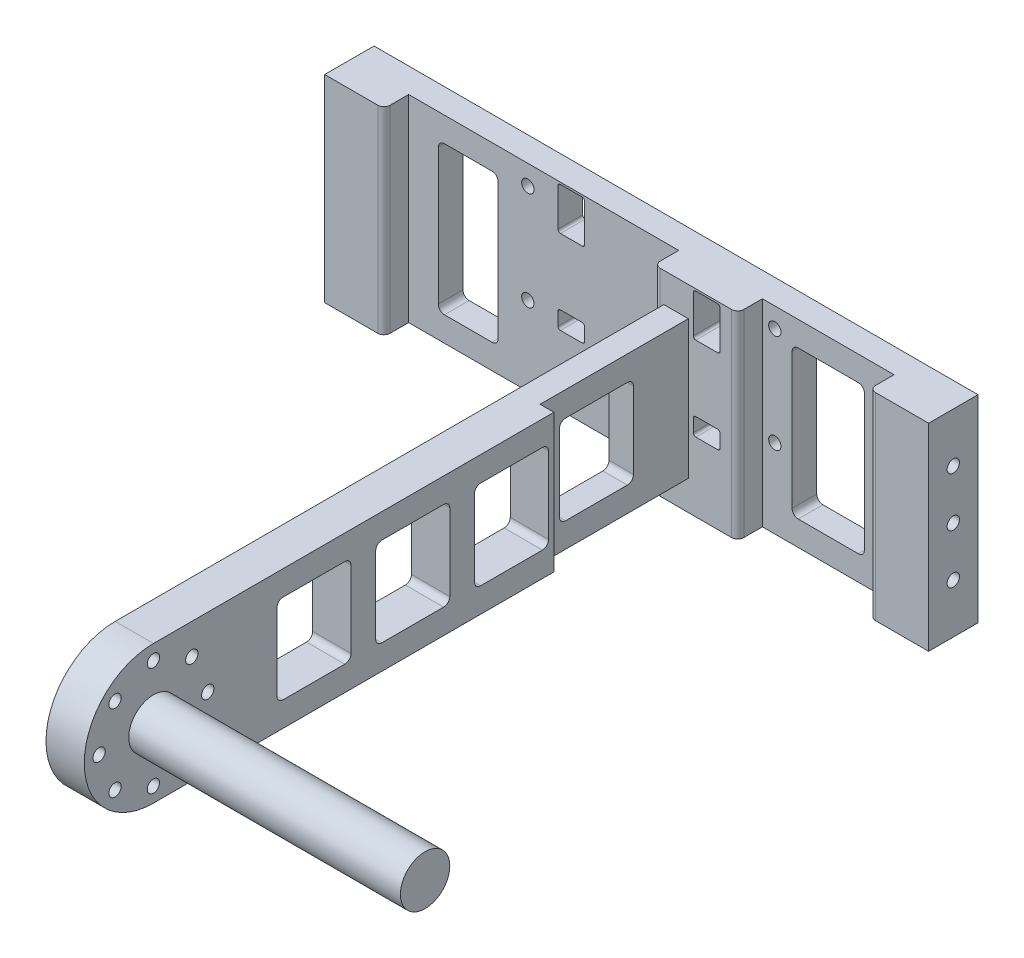
SolidWorks part; units mm, degrees
ref_plane "Front Plane" through (0, 0, 0) normal (0, 0, 1) x (1, 0, 0)
ref_plane "Top Plane" through (0, 0, 0) normal (0, 1, 0) x (1, 0, 0)
ref_plane "Right Plane" through (0, 0, 0) normal (1, 0, 0) x (0, 0, -1)
sketch "Sketch1" plane through (0, 0, 0) normal (0, 0, 1) x (1, 0, 0)
  line L1 (0, 0) -> (122.28, 0)
  line L2 (0, 0) -> (0, 40)
  line L3 (0, 40) -> (122.28, 40)
  line L4 (122.28, 0) -> (122.28, 40)
  dimension "D1" = 40
  dimension "D2" = 122.28
extrude "Boss-Extrude1" add sketch "Sketch1" along normal blind 10 contours L3 L4 L1 L2
sketch "Sketch2" plane through (0, 0, 10) normal (0, 0, 1) x (1, 0, 0)
  circle A0 centre (61.14, 20) radius 3.05
  circle A1 centre (76.14, 32.5) radius 1.25
  circle A2 centre (76.14, 15.5) radius 1.25
  dimension "D1" = 6.1
  dimension "D3" = 2.5
  dimension "D4" = 2.5
  dimension "D6" = 17
  dimension "D7" = 15
  dimension "D8" = 12.5
extrude "Cut-Extrude1" cut sketch "Sketch2" against normal blind 10
ref_plane "Plane1" through (61.14, 0, 0) normal (-1, 0, 0) x (0, 0, 1)
mirror "Mirror1" about plane through (61.14, 0, 0) normal (-1, 0, 0) of "Cut-Extrude1"
sketch "Sketch3" plane through (0, 0, 0) normal (-1, 0, 0) x (0, 0, 1)
  line L0 (10, 0) -> (10, 40) construction
  line L1 (10, 40) -> (0, 40) construction
  circle A0 centre (5, 20) radius 1.25
  circle A1 centre (5, 30) radius 1.25
  circle A2 centre (5, 10) radius 1.25
  dimension "D1" = 2.5
  dimension "D2" = 2.5
  dimension "D3" = 2.5
  dimension "D4" = 10
  dimension "D5" = 5
  dimension "D6" = 20
  dimension "D7" = 10
extrude "Cut-Extrude2" cut sketch "Sketch3" against normal blind 10
mirror "Mirror2" about plane through (61.14, 0, 0) normal (-1, 0, 0) of "Cut-Extrude2"
ref_plane "Plane2" through (76.43, 0, 0) normal (1, 0, 0) x (0, 0, -1)
sketch "Sketch4" plane through (76.43, 0, 0) normal (1, 0, 0) x (0, 0, -1)
  line L1 (-10, 0) -> (-10, 40) construction
  circle A0 centre (-121.1, 20) radius 5
  dimension "D1" = 10
  dimension "D2" = 111.1
extrude "Boss-Extrude2" add sketch "Sketch4" along normal blind 55 separate body
sketch "Sketch5" plane through (76.43, 0, 0) normal (-1, 0, 0) x (0, 0, 1)
  circle A0 centre (121.1, 20) radius 14
  dimension "D1" = 28
extrude "Boss-Extrude3" add sketch "Sketch5" along normal blind 7.75
sketch "Sketch6" plane through (68.68, 0, 0) normal (-1, 0, 0) x (0, 0, 1)
  circle A0 centre (121.1, 20) radius 5.05
  dimension "D1" = 10.1
ref_point "Point1"
ref_axis "Axis1" through (68.68, 20, 121.1) along (-1, 0, 0)
sketch "Sketch8" plane through (68.68, 0, 0) normal (-1, 0, 0) x (0, 0, 1)
  circle A0 centre (121.1, 9) radius 1.25
  circle A1 centre (121.1, 20) radius 14 construction
  dimension "D1" = 2.5
  dimension "D2" = 11
ref_plane "Plane3" through (0, 6, 0) normal (0, -1, 0) x (-1, 0, 0)
sketch "Sketch10" plane through (0, 6, 0) normal (0, -1, 0) x (-1, 0, 0)
  line L0 (-76.43, -107.1) -> (-76.43, -135.1) construction
  line L1 (-76.43, -121.1) -> (-68.68, -121.1)
  line L2 (-76.43, -121.1) -> (-76.43, -10)
  line L3 (-76.43, -10) -> (-68.68, -10)
  line L4 (-68.68, -121.1) -> (-68.68, -10)
  line L5 (0, -10) -> (-122.28, -10) construction
  dimension "D1" = 7.75
extrude "Boss-Extrude4" add sketch "Sketch10" against normal blind 28
extrude "Cut-Extrude6" cut sketch "Sketch8" against normal up to next
pattern_circular "CirPattern2" count 8 over 360 about axis through (68.68, 20, 121.1) along (-1, 0, 0) of "Cut-Extrude6"
extrude "Cut-Extrude7" cut sketch "Sketch6" against normal blind 2
sketch "Sketch11" plane through (70.68, 0, 0) normal (-1, 0, 0) x (0, 0, 1)
  circle A0 centre (121.1, 20) radius 2.675
  dimension "D1" = 5.35
extrude "Cut-Extrude8" cut sketch "Sketch11" against normal blind 3
sketch "Sketch14" plane through (76.43, 0, 0) normal (1, 0, 0) x (0, 0, -1)
  line L0 (-10, 34) -> (-121.1, 34) construction
  line L1 (-10, 34) -> (-40, 34)
  line L2 (-10, 34) -> (-10, 6)
  line L3 (-10, 6) -> (-40, 6)
  line L4 (-40, 34) -> (-40, 6)
  line L5 (-10, 6) -> (-121.1, 6) construction
  line L6 (-10, 31.2841) -> (-10, 16.7159) construction
  dimension "D1" = 30
  dimension "D2" = 0
extrude "Cut-Extrude10" cut sketch "Sketch14" against normal blind 2.8
sketch "Sketch15" plane through (0, 0, 0) normal (0, 0, -1) x (-1, 0, 0)
  circle A0 centre (-86.14, 16) radius 1.25
  circle A1 centre (-61.14, 20) radius 3.05 construction
  circle A2 centre (-86.14, 36) radius 1.25
  dimension "D1" = 2.5
  dimension "D2" = 25
  dimension "D3" = 4
  dimension "D4" = 2.5
  dimension "D5" = 16
extrude "Cut-Extrude11" cut sketch "Sketch15" against normal blind 10
mirror "Mirror3" about plane through (61.14, 0, 0) normal (-1, 0, 0) of "Cut-Extrude11"
sketch "Sketch16" plane through (0, 0, 0) normal (0, 0, -1) x (-1, 0, 0)
  line L1 (-74.64, 31) -> (-80.04, 31)
  line L2 (-74.64, 31) -> (-74.64, 39.6)
  line L3 (-74.64, 39.6) -> (-80.04, 39.6)
  line L4 (-80.04, 31) -> (-80.04, 39.6)
  line L5 (-74.64, 14) -> (-80.04, 14)
  line L6 (-74.64, 14) -> (-74.64, 17.6)
  line L7 (-74.64, 17.6) -> (-80.04, 17.6)
  line L8 (-80.04, 14) -> (-80.04, 17.6)
  circle A0 centre (-61.14, 20) radius 3.05 construction
  dimension "D3" = 13.5
  dimension "D4" = 11
  dimension "D1" = 5.4
  dimension "D2" = 8.6
  dimension "D5" = 5.4
  dimension "D6" = 3.6
  dimension "D7" = 13.5
  dimension "D8" = 6
extrude "Cut-Extrude12" cut sketch "Sketch16" against normal blind 10
mirror "Mirror4" about plane through (61.14, 0, 0) normal (-1, 0, 0) of "Cut-Extrude12"
fillet "Fillet1" radius 0.5 8 edges at (74.64, 17.6, 5) (80.04, 17.6, 5) (80.04, 14, 5) (74.64, 14, 5) (42.24, 17.6, 5) (47.64, 17.6, 5) (47.64, 14, 5) (42.24, 14, 5)
fillet "Fillet2" radius 0.5 8 edges at (80.04, 31, 5) (74.64, 31, 5) (80.04, 39.6, 5) (74.64, 39.6, 5) (47.64, 39.6, 5) (42.24, 39.6, 5) (47.64, 31, 5) (42.24, 31, 5)
sketch "Sketch17" plane through (0, 0, 10) normal (0, 0, 1) x (1, 0, 0)
  line L0 (0, 40) -> (122.28, 40) construction
  line L1 (12, 0) -> (66.68, 0)
  line L2 (12, 0) -> (12, 40)
  line L3 (12, 40) -> (66.68, 40)
  line L4 (66.68, 0) -> (66.68, 40)
  line L5 (0, 0) -> (122.28, 0) construction
  line L6 (0, 0) -> (0, 40) construction
  line L8 (68.68, 34) -> (68.68, 6) construction
  dimension "D1" = 0
  dimension "D2" = 0
  dimension "D3" = 12
  dimension "D4" = 2
extrude "Cut-Extrude14" cut sketch "Sketch17" against normal blind 5 contours L1 L4 L3 L2
sketch "Sketch18" plane through (0, 0, 10) normal (0, 0, 1) x (1, 0, 0)
  line L0 (0, 0) -> (12, 0) construction
  line L1 (110.28, 0) -> (83.63, 0)
  line L2 (110.28, 0) -> (110.28, 40)
  line L3 (110.28, 40) -> (83.63, 40)
  line L4 (83.63, 0) -> (83.63, 40)
  line L5 (0, 40) -> (12, 40) construction
  line L6 (73.63, 6) -> (73.63, 34) construction
  line L7 (122.28, 0) -> (122.28, 40) construction
  dimension "D1" = 0
  dimension "D2" = 0
  dimension "D3" = 10
  dimension "D4" = 12
extrude "Cut-Extrude15" cut sketch "Sketch18" against normal blind 5
fillet "Fillet4" radius 1.25 4 edges at (12, 20, 10) (66.68, 20, 10) (83.63, 20, 10) (110.28, 20, 10)
sketch "Sketch21" plane through (68.68, 0, 0) normal (-1, 0, 0) x (0, 0, 1)
  line L0 (121.1, 34) -> (10, 34) construction
  line L1 (96.1, 29) -> (81.1, 29)
  line L2 (96.1, 29) -> (96.1, 11)
  line L3 (96.1, 11) -> (81.1, 11)
  line L4 (81.1, 29) -> (81.1, 11)
  line L5 (121.1, 6) -> (10, 6) construction
  line L7 (76.1, 29) -> (61.1, 29)
  line L8 (76.1, 29) -> (76.1, 11)
  line L9 (76.1, 11) -> (61.1, 11)
  line L10 (61.1, 29) -> (61.1, 11)
  line L11 (56.1, 29) -> (41.1, 29)
  line L12 (56.1, 29) -> (56.1, 11)
  line L13 (56.1, 11) -> (41.1, 11)
  line L14 (41.1, 29) -> (41.1, 11)
  line L15 (36.1, 29) -> (21.1, 29)
  line L16 (36.1, 29) -> (36.1, 11)
  line L17 (36.1, 11) -> (21.1, 11)
  line L18 (21.1, 29) -> (21.1, 11)
  arc A0 (121.1, 6) -> (121.1, 34) centre (121.1, 20) ccw construction
  dimension "D1" = 5
  dimension "D2" = 5
  dimension "D3" = 25
  dimension "D4" = 15
  dimension "D5" = 15
  dimension "D6" = 5
  dimension "D7" = 15
  dimension "D8" = 5
  dimension "D9" = 15
  dimension "D10" = 5
extrude "Cut-Extrude17" cut sketch "Sketch21" against normal up to next
fillet "Fillet5" radius 1.25 16 edges at (71.155, 11, 36.1) (71.155, 29, 36.1) (71.155, 29, 21.1) (71.155, 11, 21.1) (72.555, 11, 41.1) (72.555, 29, 41.1) (72.555, 29, 56.1) (72.555, 11, 56.1) (72.555, 29, 61.1) (72.555, 11, 61.1) (72.555, 11, 76.1) (72.555, 29, 76.1) (72.555, 29, 81.1) (72.555, 11, 81.1) (72.555, 11, 96.1) (72.555, 29, 96.1)
sketch "Sketch22" plane through (0, 0, 0) normal (0, 0, -1) x (-1, 0, 0)
  line L0 (-83.63, 0) -> (-110.28, 0) construction
  line L1 (-104.28, 5) -> (-89.63, 5)
  line L2 (-104.28, 5) -> (-104.28, 35)
  line L3 (-104.28, 35) -> (-89.63, 35)
  line L4 (-89.63, 5) -> (-89.63, 35)
  line L5 (-110.28, 40) -> (-83.63, 40) construction
  line L6 (-83.63, 40) -> (-83.63, 0) construction
  line L7 (-110.28, 0) -> (-110.28, 40) construction
  dimension "D1" = 5
  dimension "D2" = 5
  dimension "D3" = 6
  dimension "D4" = 6
extrude "Cut-Extrude18" cut sketch "Sketch22" against normal up to next
fillet "Fillet6" radius 1.25 4 edges at (104.28, 35, 2.5) (89.63, 35, 2.5) (89.63, 5, 2.5) (104.28, 5, 2.5)
sketch "Sketch23" plane through (0, 0, 5) normal (0, 0, 1) x (1, 0, 0)
  line L0 (12, 0) -> (12, 40) construction
  line L1 (18, 5) -> (30.14, 5)
  line L2 (18, 5) -> (18, 35)
  line L3 (18, 35) -> (30.14, 35)
  line L4 (30.14, 5) -> (30.14, 35)
  line L5 (12, 0) -> (66.68, 0) construction
  line L6 (12, 40) -> (66.68, 40) construction
  circle A0 centre (36.14, 36) radius 1.25 construction
  dimension "D1" = 6
  dimension "D2" = 5
  dimension "D3" = 5
  dimension "D4" = 6
extrude "Cut-Extrude19" cut sketch "Sketch23" against normal up to next
fillet "Fillet7" radius 1.25 4 edges at (18, 35, 2.5) (30.14, 35, 2.5) (30.14, 5, 2.5) (18, 5, 2.5)
